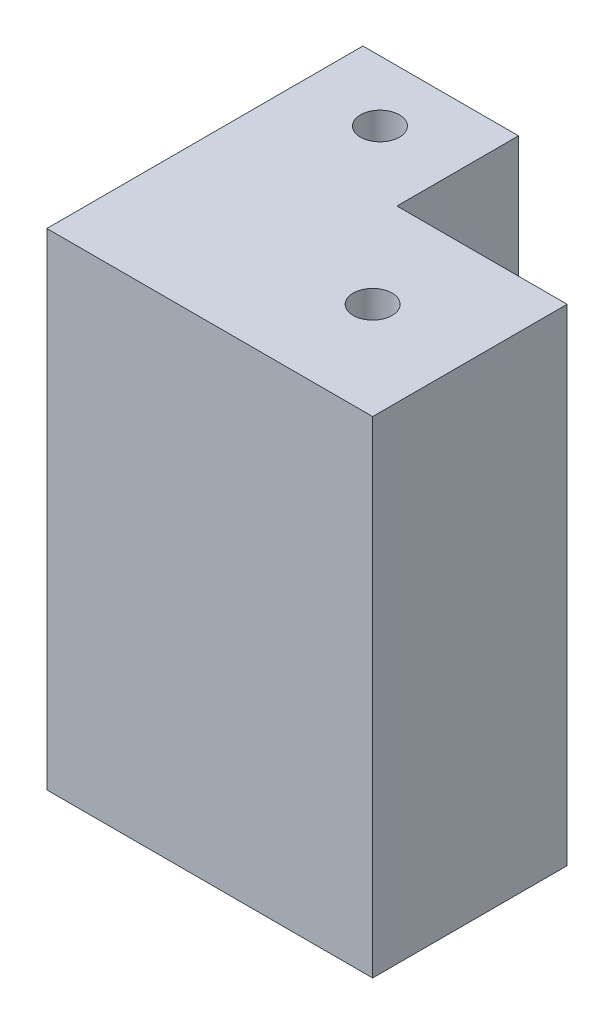
SolidWorks part; units mm, degrees
ref_plane "Front Plane" through (0, 0, 0) normal (0, 0, 1) x (1, 0, 0)
ref_plane "Top Plane" through (0, 0, 0) normal (0, 1, 0) x (1, 0, 0)
ref_plane "Right Plane" through (0, 0, 0) normal (1, 0, 0) x (0, 0, -1)
sketch "Sketch1" plane through (0, 0, 0) normal (0, 1, 0) x (1, 0, 0)
  line L0 (0, 0) -> (0, 25)
  line L1 (0, 25) -> (-32, 25)
  line L2 (-32, 25) -> (-32, -40)
  line L3 (-32, -40) -> (35, -40)
  line L4 (35, -40) -> (35, 0)
  line L5 (35, 0) -> (0, 0)
  line L6 (-32, 0) -> (0, 0) construction
  line L7 (0, -40) -> (0, 0) construction
  line L8 (0, 25) -> (-32, 0) construction
  line L9 (25, 25) -> (25, 0) construction
  line L10 (0, 25) -> (25, 25) construction
  line L11 (25, 0) -> (5, -40) construction
  line L12 (5, 5) -> (5, -40) construction
  line L13 (25, 25) -> (5, 25) construction
  line L14 (25, 25) -> (25, 5) construction
  line L15 (25, 5) -> (5, 5) construction
  line L16 (5, 25) -> (5, 5) construction
  circle A0 centre (-16, 12.5) radius 4
  circle A1 centre (15, -20) radius 4
  circle A2 centre (-16, 12.5) radius 11 construction
  circle A3 centre (-16, 12.5) radius 6 construction
  circle A4 centre (15, -20) radius 6.75 construction
  circle A5 centre (15, -20) radius 16 construction
  dimension "D4" = 8
  dimension "D5" = 22
  dimension "D6" = 12
  dimension "D7" = 13.5
  dimension "D8" = 32
  dimension "D1" = 25
  dimension "D2" = 25
  dimension "D3" = 40
  dimension "D9" = 32
  dimension "D10" = 20
  dimension "D11" = 20
extrude "Boss-Extrude1" add sketch "Sketch1" along normal blind 100
ref_plane "Plane1" through (0, 0, 0) normal (0, -1, 0) x (-1, 0, 0)
sketch "Sketch8" plane through (0, 0, 0) normal (0, -1, 0) x (-1, 0, 0)
  point P0 (-15, -20)
hole_wizard "CBORE for M5 Hex Head Bolt2" positions "Sketch8" profile "Sketch9" counterbore size "M5" standard "ANSI Metric"
sketch "Sketch9" plane through (15, 0, 20) normal (1, 0, 0) x (0, 0, -1)
  line L0 (0, 0) -> (0, 23.85)
  line L1 (0, 23.85) -> (6.75, 23.85)
  line L2 (6.75, 23.85) -> (6.75, 5)
  line L3 (6.75, 5) -> (16, 5)
  line L4 (16, 5) -> (16, 0)
  line L5 (16, 0) -> (0, 0)
  line L10 (0, 23.85) -> (-6.75, 23.85) construction
  line L11 (0, -6.35) -> (0, 107.95) construction
  dimension "Hole Dia." = 13.5
  dimension "Hole Depth" = 23.85
  dimension "C'Bore Dia." = 32
  dimension "C'Bore Depth" = 5
  dimension "Drill Angle" = 180
sketch "Sketch10" plane through (0, 0, 0) normal (0, -1, 0) x (-1, 0, 0)
  point P0 (16, 12.5)
hole_wizard "CBORE for M5 Hex Head Bolt3" positions "Sketch10" profile "Sketch11" counterbore size "M5" standard "ANSI Metric"
sketch "Sketch11" plane through (-16, 0, -12.5) normal (1, 0, 0) x (0, 0, -1)
  line L0 (0, 0) -> (0, 13.5)
  line L1 (0, 13.5) -> (5.1, 13.5)
  line L2 (5.1, 13.5) -> (5.1, 3.5)
  line L3 (5.1, 3.5) -> (11, 3.5)
  line L4 (11, 3.5) -> (11, 0)
  line L5 (11, 0) -> (0, 0)
  line L10 (0, 13.5) -> (-5.1, 13.5) construction
  line L11 (0, -6.35) -> (0, 107.95) construction
  dimension "Hole Dia." = 10.2
  dimension "Hole Depth" = 13.5
  dimension "C'Bore Dia." = 22
  dimension "C'Bore Depth" = 3.5
  dimension "Drill Angle" = 180
